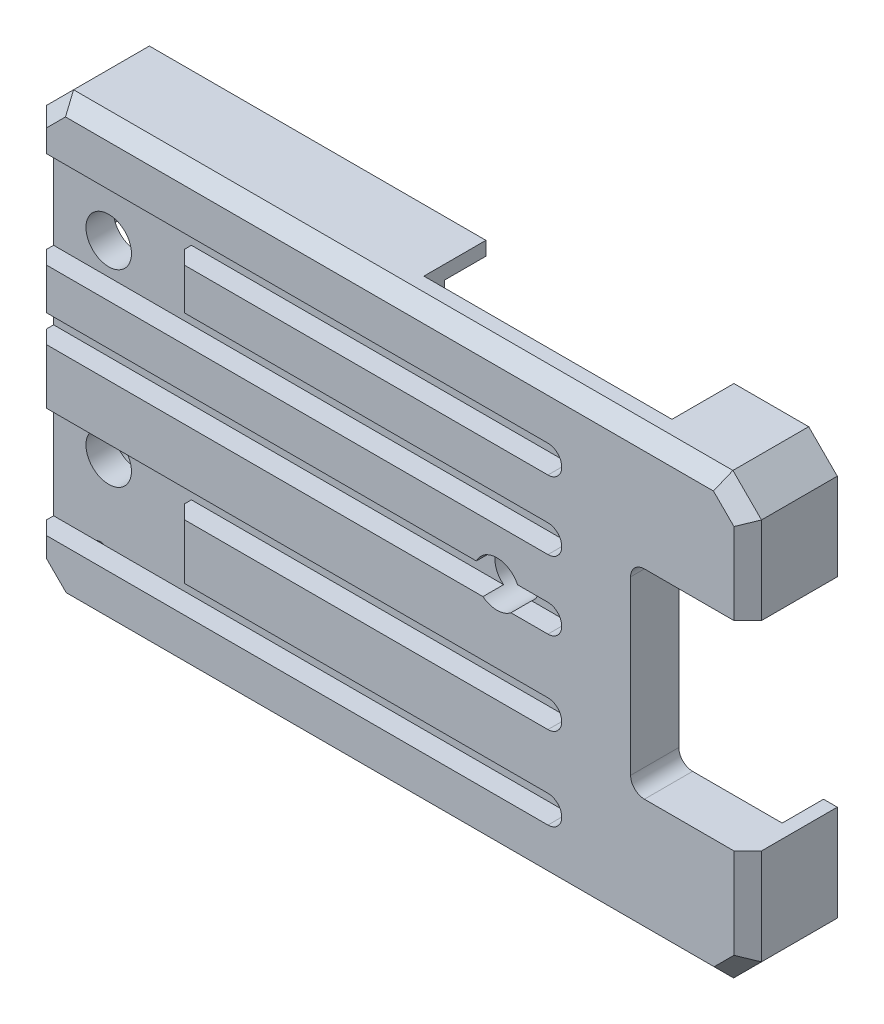
SolidWorks part; units mm, degrees
ref_plane "Спереди" through (0, 0, 0) normal (0, 0, 1) x (1, 0, 0)
ref_plane "Сверху" through (0, 0, 0) normal (0, 1, 0) x (1, 0, 0)
ref_plane "Справа" through (0, 0, 0) normal (1, 0, 0) x (0, 0, -1)
sketch "Эскиз2" plane through (0, 0, 0) normal (0, 0, 1) x (1, 0, 0)
  line L0 (-1.45, 28.425) -> (-3.4, 26.475)
  line L1 (-3.4, 26.475) -> (-3.4, -1.45)
  line L2 (-3.4, -1.45) -> (-1.4, -3.45)
  line L3 (46.45, -3.45) -> (-1.4, -3.45) construction
  line L4 (-1.4, -3.45) -> (-3.4, -1.45) construction
  line L5 (-1.4, -3.45) -> (46.45, -3.45)
  line L6 (46.45, -3.45) -> (48.475, -1.425)
  line L7 (48.475, -1.425) -> (48.475, 26.35)
  line L8 (48.475, 26.35) -> (46.4, 28.425)
  line L9 (46.4, 28.425) -> (-1.45, 28.425)
extrude "Бобышка-Вытянуть2" add sketch "Эскиз2" along normal blind 6.5
sketch "Эскиз3" plane through (0, 0, 0) normal (0, 0, -1) x (-1, 0, 0)
  line L4 (-46.4, 28.425) -> (1.45, 28.425) construction
  line L5 (-45.475, -2.45) -> (-4.6, -2.45)
  line L6 (-47.475, -0.45) -> (-47.475, 25.425)
  line L7 (-45.475, 27.425) -> (-4.6, 27.425)
  line L8 (2.4, 4.55) -> (2.4, 20.425)
  line L9 (-48.475, -1.425) -> (-48.475, 26.35) construction
  line L10 (1.4, -3.45) -> (-46.45, -3.45) construction
  line L11 (3.4, 26.475) -> (3.4, -1.45) construction
  line L12 (-2.6, 25.425) -> (-2.6, 24.425)
  line L13 (0.4, 2.55) -> (-0.6, 2.55)
  line L14 (0.4, 22.425) -> (-0.6, 22.425)
  line L15 (-2.6, 0.55) -> (-2.6, -0.45)
  arc A0 (-0.6, 2.55) -> (-2.6, 0.55) centre (-0.6, 0.55) ccw
  arc A1 (-0.6, 22.425) -> (-2.6, 24.425) centre (-0.6, 24.425) cw
  arc A2 (-2.6, 25.425) -> (-4.6, 27.425) centre (-4.6, 25.425) ccw
  arc A3 (0.4, 22.425) -> (2.4, 20.425) centre (0.4, 20.425) cw
  arc A4 (0.4, 2.55) -> (2.4, 4.55) centre (0.4, 4.55) ccw
  arc A5 (-4.6, -2.45) -> (-2.6, -0.45) centre (-4.6, -0.45) ccw
  arc A6 (-45.475, -2.45) -> (-47.475, -0.45) centre (-45.475, -0.45) cw
  arc A7 (-47.475, 25.425) -> (-45.475, 27.425) centre (-45.475, 25.425) cw
  point P18 (-2.6, 2.55)
  point P21 (-2.6, 22.425)
  point P24 (-2.6, 27.425)
  point P27 (2.4, 22.425)
  point P32 (-2.6, -2.45)
  dimension "D7" = 2
  dimension "D1" = 1
  dimension "D2" = 1
  dimension "D3" = 1
  dimension "D4" = 1
  dimension "D5" = 5
  dimension "D6" = 5
  dimension "D8" = 5
extrude "Вырез-Вытянуть1" cut sketch "Эскиз3" against normal blind 3
sketch "Эскиз4" plane through (0, 0, 0) normal (0, 0, -1) x (-1, 0, 0)
  circle A0 centre (0, 25) radius 0.5
  circle A1 centre (0, 0) radius 0.5
  dimension "D1" = 1
  dimension "D2" = 1
extrude "Вырез-Вытянуть2" cut sketch "Эскиз4" against normal blind 5
sketch "Эскиз5" plane through (0, 0, 0) normal (0, 0, -1) x (-1, 0, 0)
  line L0 (1.4, -3.45) -> (-46.45, -3.45) construction
  line L1 (-50.6373, 20.025) -> (-39.975, 20.025)
  line L2 (-50.6373, 20.025) -> (-50.6373, 5.55)
  line L3 (-50.6373, 5.55) -> (-39.975, 5.55)
  line L4 (-39.975, 20.025) -> (-39.975, 5.55)
  line L5 (-46.4, 28.425) -> (1.45, 28.425) construction
  line L6 (-48.475, -1.425) -> (-48.475, 26.35) construction
  dimension "D1" = 9
  dimension "D2" = 8.4
  dimension "D3" = 8.5
extrude "Вырез-Вытянуть3" cut sketch "Эскиз5" against normal blind 15
sketch "Эскиз6" plane through (0, 0, 0) normal (0, 0, -1) x (-1, 0, 0)
  line L1 (-40.975, 28.988) -> (-22.975, 28.988)
  line L2 (-40.975, 28.988) -> (-40.975, 22.425)
  line L3 (-40.975, 22.425) -> (-22.975, 22.425)
  line L4 (-22.975, 28.988) -> (-22.975, 22.425)
  line L5 (-48.475, 20.025) -> (-48.475, 26.35) construction
  line L6 (-46.4, 28.425) -> (1.45, 28.425) construction
  line L7 (1.4, -3.45) -> (-46.45, -3.45) construction
  line L8 (-41.075, -4.0517) -> (-22.675, -4.0517)
  line L9 (-41.075, -4.0517) -> (-41.075, 2.55)
  line L10 (-41.075, 2.55) -> (-22.675, 2.55)
  line L11 (-22.675, -4.0517) -> (-22.675, 2.55)
  line L12 (-48.475, -1.425) -> (-48.475, 5.55) construction
  dimension "D1" = 7.5
  dimension "D2" = 18
  dimension "D3" = 6
  dimension "D4" = 6
  dimension "D5" = 7.4
  dimension "D6" = 18.4
extrude "Вырез-Вытянуть4" cut sketch "Эскиз6" against normal blind 4.5
sketch "Эскиз8" plane through (0, 0, 0) normal (0, 0, -1) x (-1, 0, 0)
  line L0 (-22.975, 28.425) -> (1.45, 28.425) construction
  line L1 (5.3134, 17.625) -> (-8.6, 17.625)
  line L2 (5.3134, 17.625) -> (5.3134, 7.55)
  line L3 (5.3134, 7.55) -> (-8.6, 7.55)
  line L4 (-8.6, 17.625) -> (-8.6, 7.55)
  line L5 (1.4, -3.45) -> (-22.675, -3.45) construction
  line L6 (3.4, 26.475) -> (3.4, -1.45) construction
  dimension "D1" = 10.8
  dimension "D2" = 11
  dimension "D3" = 12
extrude "Вырез-Вытянуть5" cut sketch "Эскиз8" against normal blind 3.2
sketch "Эскиз9" plane through (0, 0, 3) normal (0, 0, -1) x (-1, 0, 0)
  line L0 (-48.475, 20.025) -> (-48.475, 26.35) construction
  line L2 (-46.4, 28.425) -> (-40.975, 28.425) construction
  line L3 (3.4, 26.475) -> (3.4, 17.625) construction
  line L4 (3.4, 7.55) -> (3.4, -1.45) construction
  line L5 (-22.975, 28.425) -> (1.45, 28.425) construction
  line L6 (1.4, -3.45) -> (-22.675, -3.45) construction
  circle A0 centre (-30.275, 13.725) radius 1.65
  circle A1 centre (-0.6, 19.725) radius 1.65
  circle A2 centre (-0.6, 6.05) radius 1.65
  point P8 (0, 0)
  point P10 (-44.445, 28.425)
  dimension "D1" = 3.3
  dimension "D2" = 18.2
  dimension "D3" = 14.7
  dimension "D4" = 4
  dimension "D5" = 4
  dimension "D6" = 8.7
  dimension "D7" = 9.5
extrude "Вырез-Вытянуть6" cut sketch "Эскиз9" against normal blind 23
chamfer "Фаска2" distance 1 angle 45 9 edges at (48.475, 2.0625, 6.5) (47.4625, -2.4375, 6.5) (22.525, -3.45, 6.5) (-2.4, -2.45, 6.5) (-3.4, 12.5125, 6.5) (-2.425, 27.45, 6.5) (22.475, 28.425, 6.5) (48.475, 23.1875, 6.5) (47.4375, 27.3875, 6.5)
fillet "Скругление1" radius 1 8 edges at (8.6, 17.625, 3.1) (8.6, 7.55, 3.1) (22.675, 2.55, 3.75) (41.075, 2.55, 3.75) (40.975, 22.425, 3.75) (22.975, 22.425, 3.75) (39.975, 5.55, 4.75) (39.975, 20.025, 4.75)
sketch "Эскиз20" plane through (0, 0, 6.5) normal (0, 0, 1) x (1, 0, 0)
  line L0 (39.975, 19.025) -> (39.975, 6.55) construction
  line L1 (-8.842, 24.425) -> (34.975, 24.425)
  line L2 (-8.842, 24.425) -> (-8.842, 22.425)
  line L3 (-8.842, 22.425) -> (34.975, 22.425)
  line L4 (34.975, 24.425) -> (34.975, 22.425)
  line L5 (-8.842, 14.425) -> (34.975, 14.425)
  line L6 (-8.842, 14.425) -> (-8.842, 12.425)
  line L7 (-8.842, 12.425) -> (34.975, 12.425)
  line L8 (34.975, 14.425) -> (34.975, 12.425)
  line L9 (-9.1513, 2.425) -> (34.975, 2.425)
  line L10 (-9.1513, 2.425) -> (-9.1513, 0.425)
  line L11 (-9.1513, 0.425) -> (34.975, 0.425)
  line L12 (34.975, 2.425) -> (34.975, 0.425)
  line L13 (-8.842, 8.425) -> (34.975, 8.425)
  line L14 (-8.842, 8.425) -> (-8.842, 6.425)
  line L15 (-8.842, 6.425) -> (34.975, 6.425)
  line L16 (34.975, 8.425) -> (34.975, 6.425)
  line L17 (-9.3869, 19.425) -> (34.975, 19.425)
  line L18 (-9.3869, 19.425) -> (-9.3869, 17.425)
  line L19 (-9.3869, 17.425) -> (34.975, 17.425)
  line L20 (34.975, 19.425) -> (34.975, 17.425)
  line L21 (-1.45, 28.425) -> (46.4, 28.425) construction
  dimension "D1" = 2
  dimension "D2" = 2
  dimension "D3" = 2
  dimension "D4" = 2
  dimension "D5" = 2
  dimension "D6" = 4
  dimension "D7" = 4
  dimension "D8" = 3
  dimension "D9" = 3
  dimension "D10" = 5
  dimension "D11" = 4
extrude "Вырез-Вытянуть7" cut sketch "Эскиз20" against normal blind 1.5
fillet "Скругление2" radius 1 10 edges at (34.975, 0.425, 5.75) (34.975, 6.425, 5.75) (34.975, 12.425, 5.75) (34.975, 17.425, 5.75) (34.975, 2.425, 5.75) (34.975, 8.425, 5.75) (34.975, 14.425, 5.75) (34.975, 19.425, 5.75) (34.975, 22.425, 5.75) (34.975, 24.425, 5.75)
sketch "Эскиз21" plane through (0, 0, 6.5) normal (0, 0, 1) x (1, 0, 0)
  line L0 (-3.4, 24.425) -> (-3.4, 22.425) construction
  line L1 (-6.6313, 23.1924) -> (6.6, 23.1924)
  line L2 (-6.6313, 23.1924) -> (-6.6313, 18.6198)
  line L3 (-6.6313, 18.6198) -> (6.6, 18.6198)
  line L4 (6.6, 23.1924) -> (6.6, 18.6198)
  line L5 (-6.0476, 7.4802) -> (6.6, 7.4802)
  line L6 (-6.0476, 7.4802) -> (-6.0476, 1.3997)
  line L7 (-6.0476, 1.3997) -> (6.6, 1.3997)
  line L8 (6.6, 7.4802) -> (6.6, 1.3997)
  line L9 (-3.4, 8.425) -> (-3.4, 6.425) construction
  dimension "D1" = 10
  dimension "D2" = 10
extrude "Вырез-Вытянуть8" cut sketch "Эскиз21" against normal blind 1.5
chamfer "Фаска3" distance 1 angle 45 2 edges at (6.6, 4.425, 6.5) (6.6, 20.925, 6.5)
equation "\"1ю5\"=2"
